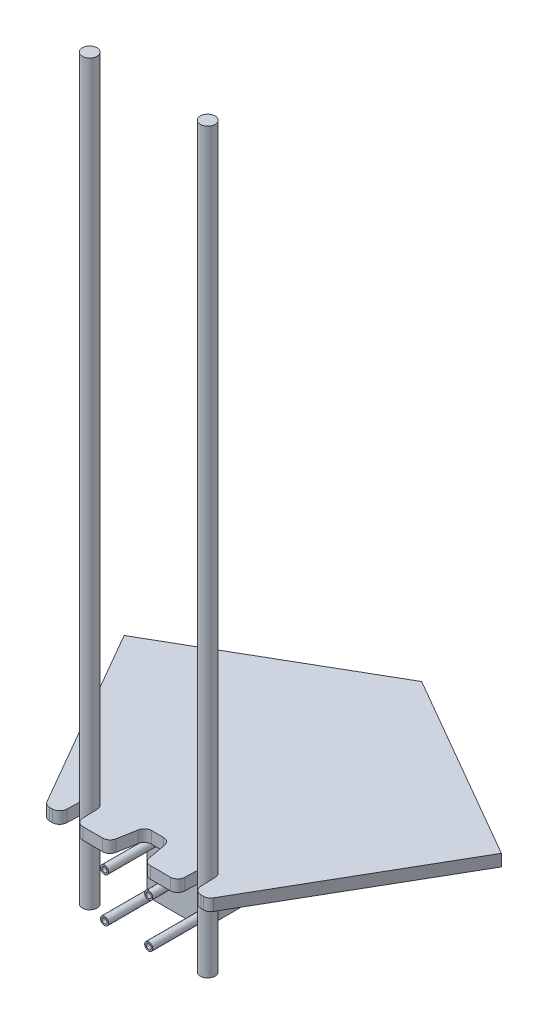
SolidWorks part; units mm, degrees
ref_plane "Front Plane" through (0, 0, 0) normal (0, 0, 1) x (1, 0, 0)
ref_plane "Top Plane" through (0, 0, 0) normal (0, 1, 0) x (1, 0, 0)
ref_plane "Right Plane" through (0, 0, 0) normal (1, 0, 0) x (0, 0, -1)
sketch "Sketch3" plane through (0, 0, 0) normal (1, 0, 0) x (0, 0, -1)
  line L0 (0, 115.8728) -> (0, -116.5666) construction
ref_axis "Axis1" through (0, 115.8728, 0) along (0, -1, 0)
ref_plane "Mirror Plane 1" through (0, 0, 0) normal (-0.5, 0, 0.866) x (0.866, 0, 0.5)
ref_plane "Mirror Plane 2" through (0, 0, 0) normal (-0.5, 0, -0.866) x (-0.866, 0, 0.5)
sketch "Sketch2" plane through (0, 0, 0) normal (0, 1, 0) x (1, 0, 0)
  line L0 (0, 0) -> (409.2328, 0) construction
  line L1 (115.4701, 200) -> (-115.4701, 200) construction
  line L2 (-115.4701, 200) -> (-230.9401, 0) construction
  line L3 (-230.9401, 0) -> (-115.4701, -200) construction
  line L4 (-115.4701, -200) -> (115.4701, -200) construction
  line L5 (115.4701, -200) -> (230.9401, 0) construction
  line L6 (230.9401, 0) -> (115.4701, 200) construction
  line L7 (-55, -200) -> (55, -200)
  line L8 (55, -200) -> (127.8525, -73.8157)
  line L9 (0, 0) -> (420.4085, -242.7229) construction
  line L10 (0, 0) -> (-311.2657, -179.7094) construction
  line L11 (0, 0) -> (0, -200) construction
  line L12 (-55, -200) -> (-127.8525, -73.8157)
  line L13 (-127.8525, -73.8157) -> (0, 0)
  line L14 (0, 0) -> (127.8525, -73.8157)
  line L15 (40, -149.1831) -> (40, -226.1143) construction
  line L16 (-40, -149.1831) -> (-40, -226.1143) construction
  circle A0 centre (0, 0) radius 200 construction
  dimension "D1" = 30
  dimension "Effective Machine Footprint" = 400
  dimension "D2" = 120
  dimension "Rod distance from corner" = 15
  dimension "Distance Between Rods" = 80
extrude "Boss-Extrude1" add sketch "Sketch2" along normal blind 8
extrude "Cut-Extrude1" cut sketch "Sketch4" against normal blind 8
sketch "Sketch4" plane through (0, 8, 0) normal (0, 1, 0) x (1, 0, 0)
  line L0 (0, 0) -> (0, -293.3675) construction
  line L1 (40, -140.894) -> (40, -265.3832) construction
  line L2 (-40, -140.894) -> (-40, -265.3832) construction
  line L3 (-55, -200) -> (55, -200) construction
  line L4 (44.997, -184.8255) -> (45.5269, -200)
  line L5 (35.003, -184.8255) -> (34.4731, -200)
  line L6 (34.4731, -200) -> (45.5269, -200)
  line L7 (-34.4731, -200) -> (-45.5269, -200)
  line L8 (-35.003, -184.8255) -> (-34.4731, -200)
  line L9 (-44.997, -184.8255) -> (-45.5269, -200)
  arc A0 (44.997, -184.8255) -> (35.003, -184.8255) centre (40, -185) ccw
  arc A1 (-44.997, -184.8255) -> (-35.003, -184.8255) centre (-40, -185) cw
  dimension "D1" = 2
  dimension "Rod Size" = 10
  dimension "Distance between rods" = 80
  dimension "Rod Distance from axis" = 15
sketch "Sketch6" plane through (0, 8, 0) normal (0, 1, 0) x (1, 0, 0)
  line L0 (-34.4731, -200) -> (34.4731, -200) construction
  line L1 (-8.25, -179) -> (-11.9529, -200)
  line L2 (-11.9529, -200) -> (0, -200)
  line L3 (-8.25, -179) -> (8.25, -179)
  line L5 (0, 0) -> (0, -314.1835) construction
  line L6 (8.25, -179) -> (11.9529, -200)
  line L7 (11.9529, -200) -> (0, -200)
  dimension "D1" = 21
  dimension "D2" = 10
  dimension "Belt Slot width" = 16.5
extrude "Cut-Extrude2" cut sketch "Sketch6" against normal blind 8
fillet "Fillet1" radius 5 10 edges at (45.5269, 4, 200) (34.4731, 4, 200) (-34.4731, 4, 200) (-45.5269, 4, 200) (-55, 4, 200) (55, 4, 200) (-11.9529, 4, 200) (-8.25, 4, 179) (11.9529, 4, 200) (8.25, 4, 179)
sketch "Sketch5" plane through (0, 0, 0) normal (0, 1, 0) x (1, 0, 0)
  line L0 (0, 0) -> (0, -293.9686) construction
  circle A0 centre (40, -185) radius 5
  circle A1 centre (-40, -185) radius 5
  dimension "D1" = 10
extrude "Boss-Extrude2" add sketch "Sketch5" along normal blind 450 and the other way blind 50 separate body
sketch "Sketch7" plane through (0, 0, 200) normal (0, 0, 1) x (1, 0, 0)
  line L0 (-111.7987, -25) -> (124.8923, -25) construction
  line L1 (-140.1448, 0) -> (162.1129, 0) construction
  line L2 (0, 0) -> (0, -55.0803) construction
  circle A0 centre (-15, -10) radius 1.75
  circle A1 centre (-15, -40) radius 1.75
  circle A2 centre (15, -40) radius 1.75
  circle A3 centre (15, -10) radius 1.75
  circle A4 centre (-15, -10) radius 2.75
  circle A5 centre (-15, -40) radius 2.75
  circle A6 centre (15, -40) radius 2.75
  circle A7 centre (15, -10) radius 2.75
  dimension "D4" = 3.5
  dimension "D5" = 1
  dimension "D1" = 25
  dimension "D2" = 30
  dimension "D3" = 30
extrude "Boss-Extrude3" add sketch "Sketch7" against normal blind 35 separate body
sketch "Sketch8" plane through (0, 0, 165) normal (0, 0, -1) x (-1, 0, 0)
  line L0 (-168.024, -25) -> (138.1293, -25) construction
  line L1 (0, 0) -> (0, -126.5043) construction
  line L2 (0, 115.8728) -> (0, -116.5666) construction
  line L3 (-163.9769, 0) -> (142.1764, 0) construction
  line L5 (-21.15, -3.85) -> (21.15, -3.85)
  line L6 (-21.15, -3.85) -> (-21.15, -46.15)
  line L7 (-21.15, -46.15) -> (21.15, -46.15)
  line L8 (21.15, -3.85) -> (21.15, -46.15)
  circle A0 centre (-15, -10) radius 1.5
  circle A1 centre (-15, -40) radius 1.5
  circle A2 centre (15, -40) radius 1.5
  circle A3 centre (15, -10) radius 1.5
  dimension "D4" = 3
  dimension "D1" = 25
  dimension "D2" = 42.3
  dimension "D3" = 42.3
extrude "Boss-Extrude4" add sketch "Sketch8" along normal blind 40 separate body
chamfer "Chamfer1" distance 4 angle 45 4 edges at (-21.15, -3.85, 145) (-21.15, -46.15, 145) (21.15, -3.85, 145) (21.15, -46.15, 145)
equation "\"Distance between rods@Sketch4\" = \"Rod Separation Distance\""
equation "\"Rod Diameter\" = 10'#Diameter of rods on each axis"
equation "\"Machine Footprint Diameter\" = 400'#Diameter of 3 main axis"
equation "\"Rod Separation Distance\" = 80'#Distance in mm between Rods on each axis"
equation "\"Machine Footprint Height\" = 550'#Distance in mm of overall machine height"
equation "\"Rod Distance From Back\" = 15'#Distance in mm from center of each rod to the back wall"
equation "\"Rod Distance From Side\" = 15'#Distance in mm from center of each wall to sidewall"
equation "\"Effective Machine Footprint@Sketch2\" = \"Machine Footprint Diameter\""
equation "\"Distance Between Rods@Sketch2\" = \"Rod Separation Distance\""
equation "\"Rod distance from corner@Sketch2\" = \"Rod Distance From Side\""
equation "\"Rod Size@Sketch4\" = \"Rod Diameter\""
equation "\"Rod Distance from axis@Sketch4\" = \"Rod Distance From Back\""
equation "\"Acrylic Hole Clearance\" = 0.25'#Clearance in lasercut parts if needed"
equation "\"Rod Slot Draft Angle\"= 2'#angle in degrees of slots in lasercut parts"
equation "\"D1@Sketch4\" = \"Rod Slot Draft Angle\""
equation "\"Base Thickness\"= 8'#thickness of lasercut base in mm"
equation "\"Top Thickness\"= 8'#thickness of lasercut top"
equation "\"Bottom Thickness\"= 8'#thickness of lasercut bottom in mm"
equation "\"D1@Boss-Extrude1\" = \"Base Thickness\""
equation "\"D1@Cut-Extrude1\"= \"Base Thickness\""
equation "\"Belt Width\"= 10'#belt width in mm"
equation "\"Belt Thickness\"= 2'#belt thickness in mm"
equation "\"Pulley Outer Diameter\"= 14.5'#outer diameter of pulley in mm"
equation "\"Belt Slot width@Sketch6\" = \"Pulley Outer Diameter\" + 2"
equation "\"Base Belt Slot Draft\" = 10'#draft in deg. of belt slot in base"
equation "\"Rod Length\"= 500'# length in mm of rods"
equation "\"Motor Width/Height\"= 42.3'#width height of nema stepper motor"
equation "\"Motor Shaft Size\"= 5'#diameter of motor shaft"
equation "\"Motor Hole Diameter\"= 3'#diameter of motor mounting holes"
equation "\"Motor Hole Width/Height\"= 30'#distance between holes x&y on stepper motor"
equation "\"D1@Sketch6\"=\"Rod Distance From Back\" + 1/2 * \"Belt Width\" + 1"
equation "\"D2@Sketch6\"=\"Base Belt Slot Draft\""
equation "\"D1@Cut-Extrude2\" = \"Base Thickness\""
equation "\"Electronics Bay Height\" = 50'#height of enclosed electronics area"
equation "\"D1@Boss-Extrude2\" = \"Rod Length\" - \"Electronics Bay Height\""
equation "\"D2@Boss-Extrude2\" = \"Electronics Bay Height\""
equation "\"D1@Sketch5\" = \"Rod Diameter\""
equation "\"Motor Standoff Length\"= 35'#distance from motor face to sheetmetal"
equation "\"D1@Sketch7\" = \"Electronics Bay Height\" / 2"
equation "\"D2@Sketch7\" = \"Motor Hole Width/Height\""
equation "\"D3@Sketch7\" = \"Motor Hole Width/Height\""
equation "\"D1@Boss-Extrude3\" = \"Motor Standoff Length\""
equation "\"D4@Sketch7\" = \"Motor Standoff ID\""
equation "\"Motor Standoff Wall Thickness\"= 1'# wall thickness of motor standoffs"
equation "\"D5@Sketch7\" = \"Motor Standoff Wall Thickness\""
equation "\"D1@Sketch8\" = \"Electronics Bay Height\" / 2"
equation "\"D2@Sketch8\" = \"Motor Width/Height\""
equation "\"D3@Sketch8\" = \"Motor Width/Height\""
equation "\"Motor Standoff ID\" = 3.5'# inner diameter of motor standoffs"
equation "\"D4@Sketch8\" = \"Motor Hole Diameter\""
equation "\"Motor Length\" = 40'#length of body of motor"
equation "\"D1@Boss-Extrude4\" = \"Motor Length\""
